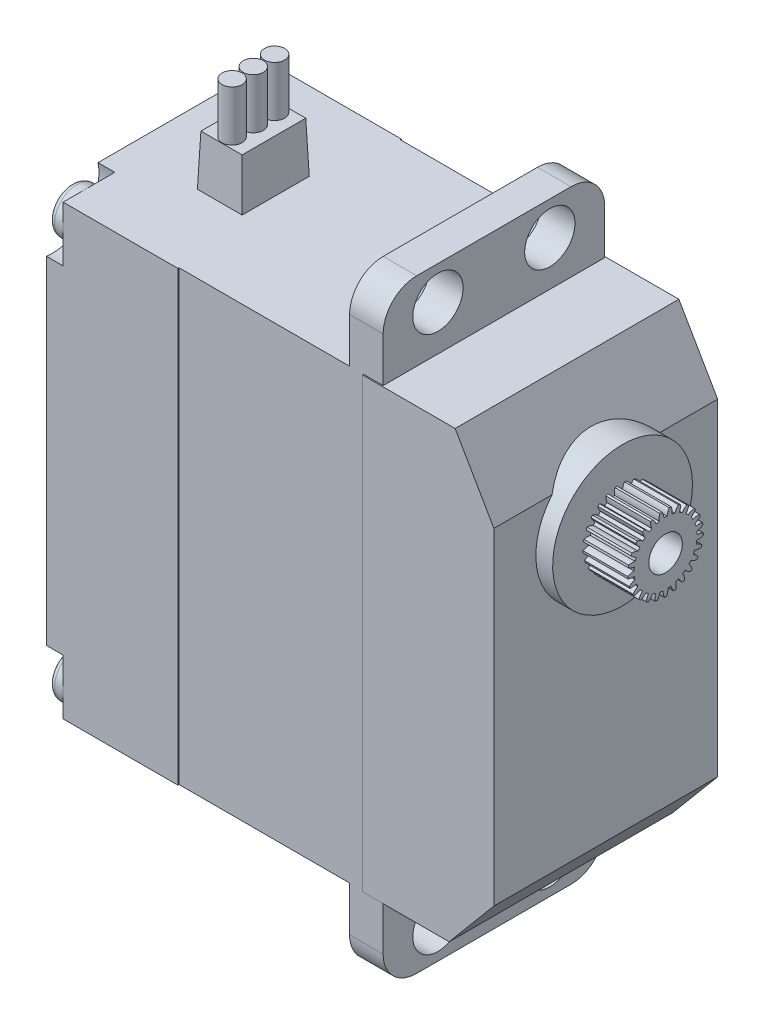
SolidWorks part; units mm, degrees
ref_plane "前视基准面" through (0, 0, 0) normal (0, 0, 1) x (1, 0, 0)
ref_plane "上视基准面" through (0, 0, 0) normal (0, 1, 0) x (1, 0, 0)
ref_plane "右视基准面" through (0, 0, 0) normal (1, 0, 0) x (0, 0, -1)
sketch "草图1" plane through (0, 0, 0) normal (0, 0, 1) x (1, 0, 0)
  line L1 (-20, -20) -> (20, -20)
  line L2 (-20, -20) -> (-20, 20)
  line L3 (-20, 20) -> (20, 20)
  line L4 (20, -20) -> (20, 20)
  line L5 (-20, -20) -> (20, 20) construction
  line L6 (-20, 20) -> (20, -20) construction
  point P0 (0, 0)
  dimension "D1" = 40
  dimension "D2" = 40
extrude "凸台-拉伸1" add sketch "草图1" along normal blind 20
ref_plane "基准面1" through (20, 0, 0) normal (1, 0, 0) x (0, 0, -1)
sketch "草图2" plane through (20, 0, 0) normal (1, 0, 0) x (0, 0, -1)
  line L0 (-10, 20) -> (-10, 10) construction
  line L1 (-20, 20) -> (0, 20) construction
  circle A0 centre (-10, 10) radius 6.25
  dimension "D2" = 12.5
  dimension "D1" = 10
extrude "凸台-拉伸2" add sketch "草图2" along normal blind 1.5
ref_plane "基准面2" through (-20, 0, 0) normal (-1, 0, 0) x (0, 0, 1)
ref_plane "基准面5" through (20, 0, 0) normal (1, 0, 0) x (0, 0, -1)
ref_plane "基准面8" through (0, 0, 0) normal (0, 0, -1) x (-1, 0, 0)
sketch "草图10" plane through (0, 0, 0) normal (0, 0, -1) x (-1, 0, 0)
  line L0 (-20, 20) -> (20, 20) construction
  line L1 (-8.25, -20) -> (8.25, -20)
  line L2 (-8.25, -20) -> (-8.25, 20)
  line L3 (-8.25, 20) -> (8.25, 20)
  line L4 (8.25, -20) -> (8.25, 20)
  line L5 (-8.25, -20) -> (8.25, 20) construction
  line L6 (-8.25, 20) -> (8.25, -20) construction
  point P0 (0, 0)
  dimension "D1" = 16.5
extrude "切除-拉伸5" cut sketch "草图10" against normal blind 0.1
ref_plane "基准面9" through (0, 0, 20) normal (0, 0, 1) x (1, 0, 0)
sketch "草图11" plane through (0, 0, 20) normal (0, 0, 1) x (1, 0, 0)
  line L0 (20, 20) -> (-20, 20) construction
  line L1 (-8.25, -20) -> (8.25, -20)
  line L2 (-8.25, -20) -> (-8.25, 20)
  line L3 (-8.25, 20) -> (8.25, 20)
  line L4 (8.25, -20) -> (8.25, 20)
  line L5 (-8.25, -20) -> (8.25, 20) construction
  line L6 (-8.25, 20) -> (8.25, -20) construction
  point P0 (0, 0)
  dimension "D1" = 16.5
extrude "切除-拉伸6" cut sketch "草图11" against normal blind 0.1
ref_plane "基准面10" through (0, 20, 0) normal (0, 1, 0) x (1, 0, 0)
ref_plane "基准面11" through (0, -20, 0) normal (0, -1, 0) x (-1, 0, 0)
ref_plane "基准面12" through (21.5, 0, 0) normal (1, 0, 0) x (0, 0, -1)
sketch "草图14" plane through (21.5, 0, 0) normal (1, 0, 0) x (0, 0, -1)
  arc A0 (-9.0018, 13.0728) -> (-9.3214, 12.5861) centre (-8.1454, 12.1623) ccw
  arc A1 (-9.3214, 12.5861) -> (-9.5931, 12.6558) centre (-10.1556, 9.9012) ccw
  arc A2 (-9.5931, 12.6558) -> (-9.6387, 13.2363) centre (-10.8278, 12.851) ccw
  arc A3 (-9.6387, 13.2363) -> (-9.8268, 13.2601) centre (-10.1556, 9.9012) ccw
  arc A4 (-9.8268, 13.2601) -> (-10.0153, 12.7092) centre (-8.7709, 12.5912) ccw
  arc A5 (-10.0153, 12.7092) -> (-10.2958, 12.7092) centre (-10.1556, 9.9012) ccw
  arc A6 (-10.2958, 12.7092) -> (-10.4843, 13.2601) centre (-11.5402, 12.5912) ccw
  arc A7 (-10.4843, 13.2601) -> (-10.6725, 13.2363) centre (-10.1556, 9.9012) ccw
  arc A8 (-10.6725, 13.2363) -> (-10.718, 12.6558) centre (-9.4834, 12.851) ccw
  arc A9 (-10.718, 12.6558) -> (-10.9897, 12.5861) centre (-10.1556, 9.9012) ccw
  arc A10 (-10.9897, 12.5861) -> (-11.3093, 13.0728) centre (-12.1657, 12.1623) ccw
  arc A11 (-11.3093, 13.0728) -> (-11.4857, 13.003) centre (-10.1556, 9.9012) ccw
  arc A12 (-11.4857, 13.003) -> (-11.3854, 12.4294) centre (-10.2381, 12.9255) ccw
  arc A13 (-11.3854, 12.4294) -> (-11.6312, 12.2943) centre (-10.1556, 9.9012) ccw
  arc A14 (-11.6312, 12.2943) -> (-12.0618, 12.6863) centre (-12.6649, 11.5913) ccw
  arc A15 (-12.0618, 12.6863) -> (-12.2153, 12.5748) centre (-10.1556, 9.9012) ccw
  arc A16 (-12.2153, 12.5748) -> (-11.9755, 12.0441) centre (-10.9876, 12.81) ccw
  arc A17 (-11.9755, 12.0441) -> (-12.18, 11.8521) centre (-10.1556, 9.9012) ccw
  arc A18 (-12.18, 11.8521) -> (-12.6946, 12.1247) centre (-13.0064, 10.9142) ccw
  arc A19 (-12.6946, 12.1247) -> (-12.8155, 11.9785) centre (-10.1556, 9.9012) ccw
  arc A20 (-12.8155, 11.9785) -> (-12.4513, 11.5242) centre (-11.6848, 12.5117) ccw
  arc A21 (-12.4513, 11.5242) -> (-12.6016, 11.2873) centre (-10.1556, 9.9012) ccw
  arc A22 (-12.6016, 11.2873) -> (-13.1678, 11.4234) centre (-13.1688, 10.1734) ccw
  arc A23 (-13.1678, 11.4234) -> (-13.2485, 11.2518) centre (-10.1556, 9.9012) ccw
  arc A24 (-13.2485, 11.2518) -> (-12.7828, 10.9023) centre (-12.286, 12.0493) ccw
  arc A25 (-12.7828, 10.9023) -> (-12.8695, 10.6355) centre (-10.1556, 9.9012) ccw
  arc A26 (-12.8695, 10.6355) -> (-13.4517, 10.6265) centre (-13.1418, 9.4155) ccw
  arc A27 (-13.4517, 10.6265) -> (-13.4872, 10.4402) centre (-10.1556, 9.9012) ccw
  arc A28 (-13.4872, 10.4402) -> (-12.9492, 10.2175) centre (-12.7533, 11.452) ccw
  arc A29 (-12.9492, 10.2175) -> (-12.9668, 9.9375) centre (-10.1556, 9.9012) ccw
  arc A30 (-12.9668, 9.9375) -> (-13.5285, 9.784) centre (-12.9272, 8.6881) ccw
  arc A31 (-13.5285, 9.784) -> (-13.5166, 9.5947) centre (-10.1556, 9.9012) ccw
  arc A32 (-13.5166, 9.5947) -> (-12.9401, 9.5128) centre (-13.0574, 10.7573) ccw
  arc A33 (-12.9401, 9.5128) -> (-12.8875, 9.2372) centre (-10.1556, 9.9012) ccw
  arc A34 (-12.8875, 9.2372) -> (-13.3934, 8.9488) centre (-12.5384, 8.0369) ccw
  arc A35 (-13.3934, 8.9488) -> (-13.3348, 8.7685) centre (-10.1556, 9.9012) ccw
  arc A36 (-13.3348, 8.7685) -> (-12.756, 8.8325) centre (-13.1791, 10.0087) ccw
  arc A37 (-12.756, 8.8325) -> (-12.6366, 8.5787) centre (-10.1556, 9.9012) ccw
  arc A38 (-12.6366, 8.5787) -> (-13.0549, 8.1735) centre (-12, 7.5029) ccw
  arc A39 (-13.0549, 8.1735) -> (-12.9532, 8.0134) centre (-10.1556, 9.9012) ccw
  arc A40 (-12.9532, 8.0134) -> (-12.4086, 8.2194) centre (-13.1109, 9.2534) ccw
  arc A41 (-12.4086, 8.2194) -> (-12.2298, 8.0032) centre (-10.1556, 9.9012) ccw
  arc A42 (-12.2298, 8.0032) -> (-12.5341, 7.5068) centre (-11.3456, 7.1196) ccw
  arc A43 (-12.5341, 7.5068) -> (-12.3959, 7.3769) centre (-10.1556, 9.9012) ccw
  arc A44 (-12.3959, 7.3769) -> (-11.9195, 7.7119) centre (-12.8569, 8.5388) ccw
  arc A45 (-11.9195, 7.7119) -> (-11.6926, 7.547) centre (-10.1556, 9.9012) ccw
  arc A46 (-11.6926, 7.547) -> (-11.8639, 6.9905) centre (-10.6165, 6.911) ccw
  arc A47 (-11.8639, 6.9905) -> (-11.6977, 6.8991) centre (-10.1556, 9.9012) ccw
  arc A48 (-11.6977, 6.8991) -> (-11.3197, 7.342) centre (-12.4333, 7.9098) ccw
  arc A49 (-11.3197, 7.342) -> (-11.0588, 7.2387) centre (-10.1556, 9.9012) ccw
  arc A50 (-11.0588, 7.2387) -> (-11.0864, 6.6571) centre (-9.8584, 6.8903) ccw
  arc A51 (-11.0864, 6.6571) -> (-10.9027, 6.6099) centre (-10.1556, 9.9012) ccw
  arc A52 (-10.9027, 6.6099) -> (-10.6467, 7.1329) centre (-11.8665, 7.4059) ccw
  arc A53 (-10.6467, 7.1329) -> (-10.3683, 7.0977) centre (-10.1556, 9.9012) ccw
  arc A54 (-10.3683, 7.0977) -> (-10.2504, 6.5275) centre (-9.1189, 7.0588) ccw
  arc A55 (-10.2504, 6.5275) -> (-10.0607, 6.5275) centre (-10.1556, 9.9012) ccw
  arc A56 (-10.0607, 6.5275) -> (-9.9428, 7.0977) centre (-11.1922, 7.0588) ccw
  arc A57 (-9.9428, 7.0977) -> (-9.6645, 7.1329) centre (-10.1556, 9.9012) ccw
  arc A58 (-9.6645, 7.1329) -> (-9.4084, 6.6099) centre (-8.4447, 7.4059) ccw
  arc A59 (-9.4084, 6.6099) -> (-9.2247, 6.6571) centre (-10.1556, 9.9012) ccw
  arc A60 (-9.2247, 6.6571) -> (-9.2523, 7.2387) centre (-10.4528, 6.8903) ccw
  arc A61 (-9.2523, 7.2387) -> (-8.9915, 7.342) centre (-10.1556, 9.9012) ccw
  arc A62 (-8.9915, 7.342) -> (-8.6134, 6.8991) centre (-7.8779, 7.9098) ccw
  arc A63 (-8.6134, 6.8991) -> (-8.4472, 6.9905) centre (-10.1556, 9.9012) ccw
  arc A64 (-8.4472, 6.9905) -> (-8.6185, 7.547) centre (-9.6947, 6.911) ccw
  arc A65 (-8.6185, 7.547) -> (-8.3916, 7.7119) centre (-10.1556, 9.9012) ccw
  arc A66 (-8.3916, 7.7119) -> (-7.9153, 7.3769) centre (-7.4542, 8.5388) ccw
  arc A67 (-7.9153, 7.3769) -> (-7.777, 7.5068) centre (-10.1556, 9.9012) ccw
  arc A68 (-7.777, 7.5068) -> (-8.0814, 8.0032) centre (-8.9655, 7.1196) ccw
  arc A69 (-8.0814, 8.0032) -> (-7.9026, 8.2194) centre (-10.1556, 9.9012) ccw
  arc A70 (-7.9026, 8.2194) -> (-7.3579, 8.0134) centre (-7.2003, 9.2534) ccw
  arc A71 (-7.3579, 8.0134) -> (-7.2563, 8.1735) centre (-10.1556, 9.9012) ccw
  arc A72 (-7.2563, 8.1735) -> (-7.6745, 8.5787) centre (-8.3112, 7.5029) ccw
  arc A73 (-7.6745, 8.5787) -> (-7.5551, 8.8325) centre (-10.1556, 9.9012) ccw
  arc A74 (-7.5551, 8.8325) -> (-6.9763, 8.7685) centre (-7.132, 10.0087) ccw
  arc A75 (-6.9763, 8.7685) -> (-6.9177, 8.9488) centre (-10.1556, 9.9012) ccw
  arc A76 (-6.9177, 8.9488) -> (-7.4236, 9.2372) centre (-7.7727, 8.0369) ccw
  arc A77 (-7.4236, 9.2372) -> (-7.371, 9.5128) centre (-10.1556, 9.9012) ccw
  arc A78 (-7.371, 9.5128) -> (-6.7945, 9.5947) centre (-7.2538, 10.7573) ccw
  arc A79 (-6.7945, 9.5947) -> (-6.7826, 9.784) centre (-10.1556, 9.9012) ccw
  arc A80 (-6.7826, 9.784) -> (-7.3443, 9.9375) centre (-7.3839, 8.6881) ccw
  arc A81 (-7.3443, 9.9375) -> (-7.3619, 10.2175) centre (-10.1556, 9.9012) ccw
  arc A82 (-7.3619, 10.2175) -> (-6.8239, 10.4402) centre (-7.5578, 11.452) ccw
  arc A83 (-6.8239, 10.4402) -> (-6.8594, 10.6265) centre (-10.1556, 9.9012) ccw
  arc A84 (-6.8594, 10.6265) -> (-7.4417, 10.6355) centre (-7.1693, 9.4155) ccw
  arc A85 (-7.4417, 10.6355) -> (-7.5283, 10.9023) centre (-10.1556, 9.9012) ccw
  arc A86 (-7.5283, 10.9023) -> (-7.0626, 11.2518) centre (-8.0251, 12.0493) ccw
  arc A87 (-7.0626, 11.2518) -> (-7.1434, 11.4234) centre (-10.1556, 9.9012) ccw
  arc A88 (-7.1434, 11.4234) -> (-7.7095, 11.2873) centre (-7.1424, 10.1734) ccw
  arc A89 (-7.7095, 11.2873) -> (-7.8599, 11.5242) centre (-10.1556, 9.9012) ccw
  arc A90 (-7.8599, 11.5242) -> (-7.4957, 11.9785) centre (-8.6263, 12.5117) ccw
  arc A91 (-7.4957, 11.9785) -> (-7.6166, 12.1247) centre (-10.1556, 9.9012) ccw
  arc A92 (-7.6166, 12.1247) -> (-8.1311, 11.8521) centre (-7.3047, 10.9142) ccw
  arc A93 (-8.1311, 11.8521) -> (-8.3356, 12.0441) centre (-10.1556, 9.9012) ccw
  arc A94 (-8.3356, 12.0441) -> (-8.0959, 12.5748) centre (-9.3235, 12.81) ccw
  arc A95 (-8.0959, 12.5748) -> (-8.2493, 12.6863) centre (-10.1556, 9.9012) ccw
  arc A96 (-8.2493, 12.6863) -> (-8.6799, 12.2943) centre (-7.6462, 11.5913) ccw
  arc A97 (-8.6799, 12.2943) -> (-8.9257, 12.4294) centre (-10.1556, 9.9012) ccw
  arc A98 (-8.9257, 12.4294) -> (-8.8255, 13.003) centre (-10.0731, 12.9255) ccw
  arc A99 (-8.8255, 13.003) -> (-9.0018, 13.0728) centre (-10.1556, 9.9012) ccw
extrude "凸台-拉伸6" add sketch "草图14" along normal blind 4
ref_plane "基准面13" through (25.5, 0, 0) normal (1, 0, 0) x (0, 0, -1)
sketch "草图15" plane through (25.5, 0, 0) normal (1, 0, 0) x (0, 0, -1)
  circle A0 centre (-10.1556, 9.9012) radius 1.5
extrude "切除-拉伸9" cut sketch "草图15" against normal blind 4
ref_plane "基准面14" through (0, 20, 0) normal (0, 1, 0) x (1, 0, 0)
ref_plane "基准面15" through (-20, 0, 0) normal (-1, 0, 0) x (0, 0, 1)
chamfer "倒角2" distance 6 angle 30 1 edges at (20, 20, 10) first distance on face at (20, 0, 10)
chamfer "倒角3" distance 4 angle 50 1 edges at (20, -20, 10) first distance on face at (0, -20, 10)
ref_plane "基准面18" through (0, -20, 0) normal (0, -1, 0) x (-1, 0, 0)
sketch "草图20" plane through (0, -20, 0) normal (0, -1, 0) x (-1, 0, 0)
  line L0 (-20, 1.0461) -> (-20, -15.8444) construction
  line L2 (-20, 0) -> (-7, 0) construction
  line L3 (22, 0) -> (-22, 0) construction
  line L4 (-7, 0) -> (-7, -0.8546) construction
  line L7 (-5.9416, -19.9) -> (-4.5261, -19.9) construction
  line L9 (-6.0182, -0.1) -> (-4.3371, -0.1) construction
  line L10 (-7, -0.1) -> (-7, -19.9) construction
  line L11 (-7, -19.9) -> (-10, -19.9) construction
  line L12 (-10, -19.9) -> (-10, 0) construction
  line L13 (-10, 0) -> (-7, 0) construction
  line L14 (-10, -0.1) -> (-7, -0.1)
  line L15 (-7, -0.1) -> (-7, -19.9)
  line L16 (-7, -19.9) -> (-10, -19.9)
  line L17 (-10, -19.9) -> (-10, -0.1)
extrude "凸台-拉伸8" add sketch "草图20" along normal blind 7
sketch "草图21" plane through (0, 20, 0) normal (0, 1, 0) x (1, 0, 0)
  line L6 (7, -19.9) -> (10, -19.9)
  line L7 (7, -0.1) -> (7, -19.9)
  line L8 (10, -0.1) -> (7, -0.1)
  line L9 (10, -19.9) -> (10, -0.1)
  line L10 (7, -19.9) -> (10, -19.9)
  line L11 (7, -0.1) -> (7, -19.9)
  line L12 (10, -0.1) -> (7, -0.1)
  line L13 (10, -19.9) -> (10, -0.1)
  dimension "D1" = 0
extrude "凸台-拉伸9" add sketch "草图21" along normal blind 7
fillet "圆角4" radius 3 4 edges at (8.5, 27, 19.9) (8.5, 27, 0.1) (8.5, -27, 19.9) (8.5, -27, 0.1)
ref_plane "基准面19" through (10, 0, 0) normal (1, 0, 0) x (0, 0, -1)
sketch "草图22" plane through (10, 0, 0) normal (1, 0, 0) x (0, 0, -1)
  line L3 (-20.5235, 0) -> (-0.5503, 0) construction
  circle A0 centre (-15, 24) radius 2.25
  circle A1 centre (-5, 24) radius 2.25
  circle A2 centre (-5, -24) radius 2.25
  circle A3 centre (-15, -24) radius 2.25
extrude "切除-拉伸12" cut sketch "草图22" against normal blind 7.3
sketch "草图24" plane through (-20, 0, 0) normal (-1, 0, 0) x (0, 0, 1)
  line L0 (20, 0) -> (0, 0) construction
  line L1 (20, -22) -> (20, 22) construction
  line L2 (10, 0) -> (10, 28.881) construction
  line L3 (0, 22) -> (0, -22) construction
  line L4 (11, 20) -> (-11, 20) construction
  line L5 (0, 15.0598) -> (0, 20)
  line L6 (0, 20) -> (4.6197, 20)
  line L7 (20, 15.0598) -> (20, 20)
  line L8 (20, 20) -> (15.3803, 20)
  line L9 (0, -20) -> (4.6197, -20)
  line L10 (0, -15.0598) -> (0, -20)
  line L11 (20, -20) -> (15.3803, -20)
  line L12 (20, -15.0598) -> (20, -20)
  arc A1 (4.6197, 20) -> (0, 15.0598) centre (0.55, 19.1756) cw
  arc A2 (15.3803, 20) -> (20, 15.0598) centre (19.45, 19.1756) ccw
  arc A3 (4.6197, -20) -> (0, -15.0598) centre (0.55, -19.1756) ccw
  arc A5 (15.3803, -20) -> (20, -15.0598) centre (19.45, -19.1756) cw
extrude "切除-拉伸13" cut sketch "草图24" against normal blind 1.5
ref_plane "基准面20" through (-18.5, 0, 0) normal (-1, 0, 0) x (0, 0, 1)
sketch "草图25" plane through (-18.5, 0, 0) normal (-1, 0, 0) x (0, 0, 1)
  line L0 (0, 0) -> (20, 0) construction
  line L1 (20, -6.4625) -> (20, 6.4625) construction
  line L2 (10, 0) -> (10, 8.1993) construction
  circle A0 centre (2.0399, 17.9472) radius 2
  circle A1 centre (17.9601, 17.9472) radius 2
  circle A2 centre (2.0399, -17.9472) radius 2
  circle A3 centre (17.9601, -17.9472) radius 2
extrude "凸台-拉伸10" add sketch "草图25" along normal blind 1.3
fillet "圆角5" radius 0.5 4 edges at (-19.8, -17.9472, 19.9601) (-19.8, -17.9472, 0.0399) (-19.8, 17.9472, 15.9601) (-19.8, 17.9472, 4.0399)
ref_plane "基准面21" through (-19.8, 0, 0) normal (-1, 0, 0) x (0, 0, 1)
sketch "草图26" plane through (-19.8, 0, 0) normal (-1, 0, 0) x (0, 0, 1)
  line L0 (1.6399, 18.3472) -> (0.5942, 18.3472)
  line L1 (1.6399, 16.5015) -> (2.4399, 16.5015)
  line L2 (1.6399, 16.5015) -> (1.6399, 17.5472)
  line L3 (1.6399, 19.3929) -> (2.4399, 19.3929)
  line L4 (2.4399, 16.5015) -> (2.4399, 17.5472)
  line L5 (1.6399, 16.5015) -> (2.4399, 19.3929) construction
  line L6 (1.6399, 19.3929) -> (2.4399, 16.5015) construction
  line L7 (3.4855, 17.5472) -> (2.4399, 17.5472)
  line L8 (3.4855, 17.5472) -> (3.4855, 18.3472)
  line L9 (3.4855, 18.3472) -> (2.4399, 18.3472)
  line L10 (0.5942, 17.5472) -> (0.5942, 18.3472)
  line L11 (3.4855, 17.5472) -> (0.5942, 18.3472) construction
  line L12 (3.4855, 18.3472) -> (0.5942, 17.5472) construction
  line L13 (2.4399, 18.3472) -> (2.4399, 19.3929)
  line L14 (1.6399, 17.5472) -> (0.5942, 17.5472)
  line L15 (1.6399, 18.3472) -> (1.6399, 19.3929)
  line L16 (0, 0) -> (20.0276, 0) construction
  line L17 (10.0138, 0) -> (10.0138, 3.4562) construction
  line L18 (16.542, 18.3472) -> (19.4334, 17.5472) construction
  line L19 (16.542, 17.5472) -> (19.4334, 18.3472) construction
  line L20 (18.3877, 19.3929) -> (17.5877, 16.5015) construction
  line L21 (18.3877, 16.5015) -> (17.5877, 19.3929) construction
  line L22 (18.3877, 18.3472) -> (18.3877, 19.3929)
  line L23 (18.3877, 17.5472) -> (19.4334, 17.5472)
  line L24 (17.5877, 18.3472) -> (17.5877, 19.3929)
  line L25 (19.4334, 17.5472) -> (19.4334, 18.3472)
  line L26 (16.542, 18.3472) -> (17.5877, 18.3472)
  line L27 (16.542, 17.5472) -> (16.542, 18.3472)
  line L28 (16.542, 17.5472) -> (17.5877, 17.5472)
  line L29 (17.5877, 16.5015) -> (17.5877, 17.5472)
  line L30 (18.3877, 19.3929) -> (17.5877, 19.3929)
  line L31 (18.3877, 16.5015) -> (18.3877, 17.5472)
  line L32 (18.3877, 16.5015) -> (17.5877, 16.5015)
  line L33 (18.3877, 18.3472) -> (19.4334, 18.3472)
  line L34 (18.3877, -16.5015) -> (17.5877, -19.3929) construction
  line L35 (18.3877, -19.3929) -> (17.5877, -16.5015) construction
  line L36 (16.542, -17.5472) -> (19.4334, -18.3472) construction
  line L37 (16.542, -18.3472) -> (19.4334, -17.5472) construction
  line L38 (3.4855, -18.3472) -> (0.5942, -17.5472) construction
  line L39 (3.4855, -17.5472) -> (0.5942, -18.3472) construction
  line L40 (1.6399, -19.3929) -> (2.4399, -16.5015) construction
  line L41 (1.6399, -16.5015) -> (2.4399, -19.3929) construction
  line L42 (18.3877, -18.3472) -> (19.4334, -18.3472)
  line L43 (18.3877, -16.5015) -> (17.5877, -16.5015)
  line L44 (18.3877, -16.5015) -> (18.3877, -17.5472)
  line L45 (18.3877, -19.3929) -> (17.5877, -19.3929)
  line L46 (17.5877, -16.5015) -> (17.5877, -17.5472)
  line L47 (16.542, -17.5472) -> (17.5877, -17.5472)
  line L48 (16.542, -17.5472) -> (16.542, -18.3472)
  line L49 (16.542, -18.3472) -> (17.5877, -18.3472)
  line L50 (19.4334, -17.5472) -> (19.4334, -18.3472)
  line L51 (17.5877, -18.3472) -> (17.5877, -19.3929)
  line L52 (18.3877, -17.5472) -> (19.4334, -17.5472)
  line L53 (18.3877, -18.3472) -> (18.3877, -19.3929)
  line L54 (1.6399, -18.3472) -> (1.6399, -19.3929)
  line L55 (1.6399, -17.5472) -> (0.5942, -17.5472)
  line L56 (2.4399, -18.3472) -> (2.4399, -19.3929)
  line L57 (0.5942, -17.5472) -> (0.5942, -18.3472)
  line L58 (3.4855, -18.3472) -> (2.4399, -18.3472)
  line L59 (3.4855, -17.5472) -> (3.4855, -18.3472)
  line L60 (3.4855, -17.5472) -> (2.4399, -17.5472)
  line L61 (2.4399, -16.5015) -> (2.4399, -17.5472)
  line L62 (1.6399, -19.3929) -> (2.4399, -19.3929)
  line L63 (1.6399, -16.5015) -> (1.6399, -17.5472)
  line L64 (1.6399, -16.5015) -> (2.4399, -16.5015)
  line L65 (1.6399, -18.3472) -> (0.5942, -18.3472)
  circle A0 centre (2.0399, 17.9472) radius 1.5 construction
  point P0 (2.0399, 17.9472)
  point P8 (2.0399, 17.9472)
  point P34 (17.9877, 17.9472)
  point P59 (17.9877, -17.9472)
  point P60 (2.0399, -17.9472)
extrude "切除-拉伸14" cut sketch "草图26" against normal blind 0.8 draft 16
ref_plane "基准面22" through (0, 20, 0) normal (0, 1, 0) x (1, 0, 0)
sketch "草图28" plane through (0, 20, 0) normal (0, 1, 0) x (1, 0, 0)
  line L0 (-20, 0) -> (-20, -20) construction
  line L1 (-20, 11) -> (-20, -11) construction
  line L2 (-6.4625, -20) -> (6.4625, -20) construction
  line L3 (-20, -10) -> (-10.9126, -10) construction
  line L4 (-20, -10) -> (-9.5, -10) construction
  line L5 (-9.5, -10) -> (-9.5, -7)
  line L6 (-9.5, -7) -> (-13.5, -7)
  line L7 (-13.5, -7) -> (-13.5, -13)
  line L8 (-13.5, -13) -> (-9.5, -13)
  line L9 (-9.5, -13) -> (-9.5, -10)
extrude "凸台-拉伸11" add sketch "草图28" along normal blind 4.5 draft 2
ref_plane "基准面23" through (0, 24.5, 0) normal (0, 1, 0) x (1, 0, 0)
sketch "草图29" plane through (0, 24.5, 0) normal (0, 1, 0) x (1, 0, 0)
  line L0 (-11.5, -7.1571) -> (-11.5, -14.7571) construction
  line L1 (-9.6571, -7.1571) -> (-13.3429, -7.1571) construction
  line L2 (-11.5, -10.9571) -> (-11.5, -7.1571) construction
  line L3 (-11.5, -10.9571) -> (-11.5, -12.8429) construction
  line L4 (-13.3429, -12.8429) -> (-9.6571, -12.8429) construction
  circle A0 centre (-11.5, -11.9) radius 0.9
  circle A1 centre (-11.5, -8.1) radius 0.9
  circle A2 centre (-11.5, -10.0025) radius 0.9
extrude "凸台-拉伸12" add sketch "草图29" along normal blind 4.5
